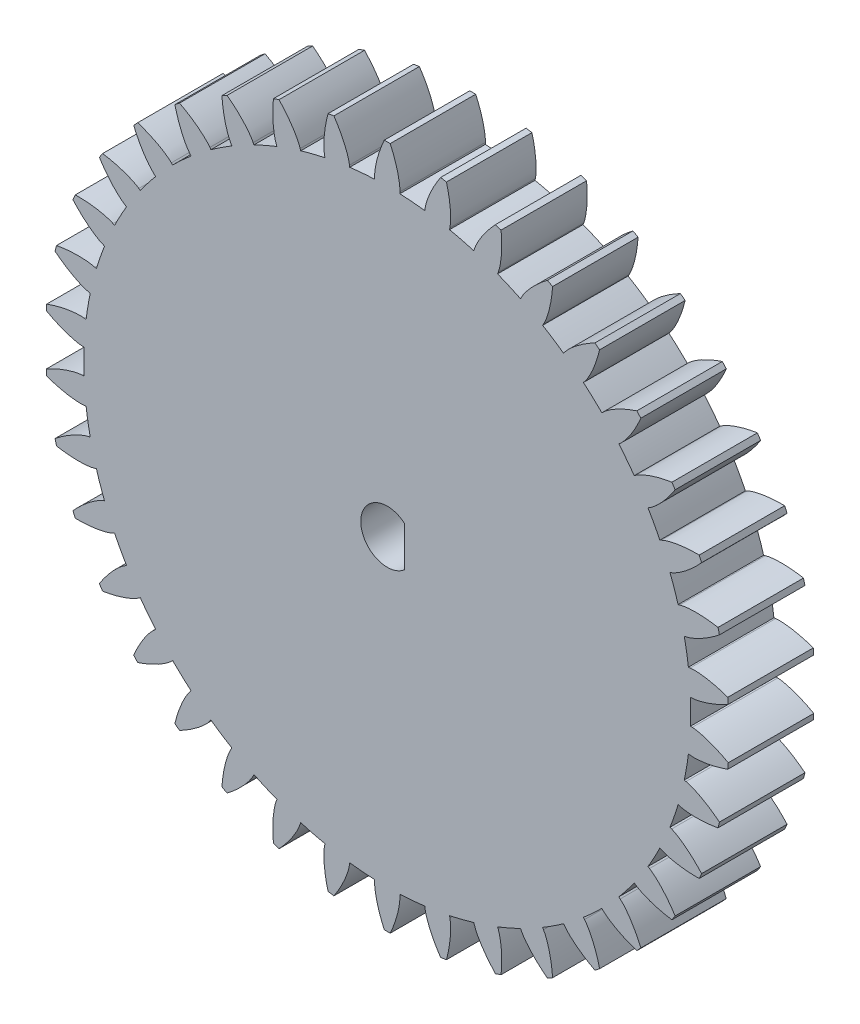
SolidWorks part; units mm, degrees
ref_plane "前视基准面" through (0, 0, 0) normal (0, 0, 1) x (1, 0, 0)
ref_plane "上视基准面" through (0, 0, 0) normal (0, 1, 0) x (1, 0, 0)
ref_plane "右视基准面" through (0, 0, 0) normal (1, 0, 0) x (0, 0, -1)
other "Configuration Table"
sketch "草图1" plane through (0, 0, 0) normal (0, 0, 1) x (1, 0, 0)
  line L0 (0, 0) -> (4, 0) construction
  line L1 (0, 0) -> (3.9231, 0.7804) construction
  line L2 (0, 0) -> (3.6941, 0.6945)
  line L3 (3.9231, 0.7804) -> (3.9231, -0.7804) construction
  line L4 (0, 0) -> (3.6941, -0.6945)
  circle A0 centre (0, 0) radius 5
  circle A1 centre (0, 0) radius 4 construction
  circle A2 centre (0, 0) radius 2.75
  circle A3 centre (0, 0) radius 3.7588 construction
  circle A4 centre (0, 0) radius 1.5
  spline S0 degree 4 poles (3.6941, 0.6945) (3.7222, 0.6998) (3.7997, 0.7204) (3.9403, 0.7826) (4.1522, 0.9137) (4.3976, 1.1246) (4.671, 1.4371) (4.933, 1.8476) (5.1531, 2.335) (5.3561, 3.0262) (5.443, 3.7431) (5.4253, 4.4924) (5.2827, 5.3729) (5.0281, 6.2292) (4.5902, 7.1708) (3.9479, 8.1289) (3.1749, 8.9843) (2.2938, 9.7273) (1.3255, 10.3516) (0.2887, 10.8537) (-0.7988, 11.2323) (-1.7817, 11.4556) (-2.5647, 11.5617) (-3.139, 11.6038) (-3.4958, 11.6181) (-3.788, 11.6215) (-4.0656, 11.6193) (-4.3699, 11.6068) (-4.6041, 11.5939) (-4.8725, 11.5704) (-5.1429, 11.5429) (-5.4129, 11.5084) (-5.885, 11.4372) (-6.2665, 11.3559) (-6.6616, 11.2688) (-6.8509, 11.2136) (-6.9779, 11.1808) knots 0 0 0 0 0 0.005604 0.015718 0.02996 0.048734 0.068727 0.096889 0.125051 0.153212 0.209535 0.237696 0.271429 0.327752 0.384075 0.440398 0.496721 0.553044 0.609367 0.66569 0.722013 0.778336 0.806497 0.820578 0.834659 0.84874 0.86282 0.876901 0.890982 0.900036 0.909091 0.931818 0.954545 0.977273 1 1 1 1 1 construction
  spline S1 degree 4 poles (3.6941, 0.6945) (3.7222, 0.6998) (3.7997, 0.7204) (3.9403, 0.7826) (4.1522, 0.9137) (4.3976, 1.1246) (4.671, 1.4371) (4.933, 1.8476) (5.1531, 2.335) (5.3561, 3.0262) (5.443, 3.7431) (5.4253, 4.4924) (5.2827, 5.3729) (5.0281, 6.2292) (4.5902, 7.1708) (3.9479, 8.1289) (3.1749, 8.9843) (2.2938, 9.7273) (1.3255, 10.3516) (0.2887, 10.8537) (-0.7988, 11.2323) (-1.7817, 11.4556) (-2.5647, 11.5617) (-3.139, 11.6038) (-3.4958, 11.6181) (-3.788, 11.6215) (-4.0656, 11.6193) (-4.3699, 11.6068) (-4.6041, 11.5939) (-4.8725, 11.5704) (-5.031, 11.5543) (-5.1147, 11.5449) (-5.1564, 11.5399) knots 0 0 0 0 0 0.005604 0.015718 0.02996 0.048734 0.068727 0.096889 0.125051 0.153212 0.209535 0.237696 0.271429 0.327752 0.384075 0.440398 0.496721 0.553044 0.609367 0.66569 0.722013 0.778336 0.806497 0.820578 0.834659 0.84874 0.86282 0.876901 0.890982 0.900036 0.909091 0.909091 0.909091 0.909091 0.909091
  spline S2 degree 4 poles (3.6941, -0.6945) (3.7222, -0.6998) (3.7997, -0.7204) (3.9403, -0.7826) (4.1522, -0.9137) (4.3976, -1.1246) (4.671, -1.4371) (4.933, -1.8476) (5.1531, -2.335) (5.3561, -3.0262) (5.443, -3.7431) (5.4253, -4.4924) (5.2827, -5.3729) (5.0281, -6.2292) (4.5902, -7.1708) (3.9479, -8.1289) (3.1749, -8.9843) (2.2938, -9.7273) (1.3255, -10.3516) (0.2887, -10.8537) (-0.7988, -11.2323) (-1.7817, -11.4556) (-2.5647, -11.5617) (-3.139, -11.6038) (-3.4958, -11.6181) (-3.788, -11.6215) (-4.0656, -11.6193) (-4.3699, -11.6068) (-4.6041, -11.5939) (-4.8725, -11.5704) (-5.1429, -11.5429) (-5.4129, -11.5084) (-5.885, -11.4372) (-6.2665, -11.3559) (-6.6616, -11.2688) (-6.8509, -11.2136) (-6.9779, -11.1808) knots 0 0 0 0 0 0.005604 0.015718 0.02996 0.048734 0.068727 0.096889 0.125051 0.153212 0.209535 0.237696 0.271429 0.327752 0.384075 0.440398 0.496721 0.553044 0.609367 0.66569 0.722013 0.778336 0.806497 0.820578 0.834659 0.84874 0.86282 0.876901 0.890982 0.900036 0.909091 0.931818 0.954545 0.977273 1 1 1 1 1 construction
  spline S3 degree 4 poles (3.6941, -0.6945) (3.7222, -0.6998) (3.7997, -0.7204) (3.9403, -0.7826) (4.1522, -0.9137) (4.3976, -1.1246) (4.671, -1.4371) (4.933, -1.8476) (5.1531, -2.335) (5.3561, -3.0262) (5.443, -3.7431) (5.4253, -4.4924) (5.2827, -5.3729) (5.0281, -6.2292) (4.5902, -7.1708) (3.9479, -8.1289) (3.1749, -8.9843) (2.2938, -9.7273) (1.3255, -10.3516) (0.2887, -10.8537) (-0.7988, -11.2323) (-1.7817, -11.4556) (-2.5647, -11.5617) (-3.139, -11.6038) (-3.4958, -11.6181) (-3.788, -11.6215) (-4.0656, -11.6193) (-4.3699, -11.6068) (-4.6041, -11.5939) (-4.8725, -11.5704) (-5.031, -11.5543) (-5.1147, -11.5449) (-5.1564, -11.5399) knots 0 0 0 0 0 0.005604 0.015718 0.02996 0.048734 0.068727 0.096889 0.125051 0.153212 0.209535 0.237696 0.271429 0.327752 0.384075 0.440398 0.496721 0.553044 0.609367 0.66569 0.722013 0.778336 0.806497 0.820578 0.834659 0.84874 0.86282 0.876901 0.890982 0.900036 0.909091 0.909091 0.909091 0.909091 0.909091
  point P15 (3.9231, 0)
  dimension "齿顶圆直径" = 10
  dimension "分度圆直径" = 8
  dimension "齿根圆直径" = 5.5
  dimension "基圆直径" = 7.5175
  dimension "内孔直径" = 3
  dimension "渐近线镜像线夹角" = 11.25
extrude "凸台-拉伸1" add sketch "草图1" along normal blind 5 contours A0 | A4
extrude "切除-拉伸1" cut sketch "草图1<3>" along normal through all contours A2 S3 A0 S1 region at (4.0533, 0, 0)
sketch "草图1<3>" plane through (0, 0, 0) normal (0, 0, 1) x (1, 0, 0) same geometry as "草图1"
fillet "圆角1" radius 0.5 4 edges at (2.7027, 0.5081, 2.5) (2.7027, -0.5081, 2.5) (4.7472, 1.5696, 2.5) (4.7472, -1.5696, 2.5)
pattern_circular "阵列(圆周)1" count 8 every 45 about axis through (0, 0, 5) along (0, 0, 1) of "切除-拉伸1", "圆角1"
sketch "草图2" plane through (0, 0, 5) normal (0, 0, 1) x (1, 0, 0)
  line L0 (0, 0) -> (19, 0) construction
  line L1 (0, 0) -> (17.8389, 0.7378)
  line L2 (0, 0) -> (17.8389, -0.7378)
  line L3 (17.8389, 0.7378) -> (17.8389, -0.7378) construction
  circle A0 centre (0, 0) radius 19 construction
  circle A1 centre (0, 0) radius 17.8542 construction
  circle A2 centre (0, 0) radius 17.75
  circle A3 centre (0, 0) radius 20
  circle A4 centre (0, 0) radius 1.5
  spline S0 degree 4 poles (17.8389, -0.7378) (17.8728, -0.7392) (17.9406, -0.7441) (18.0752, -0.7621) (18.3288, -0.8123) (18.6635, -0.9051) (19.1205, -1.0702) (19.658, -1.3153) (20.4669, -1.7609) (21.5195, -2.5027) (22.8507, -3.7145) (24.3091, -5.5094) (25.6114, -7.6908) (26.6766, -10.2121) (27.4216, -12.8444) (27.8645, -15.543) (28.0306, -18.4074) (27.8656, -21.9567) (27.1273, -26.1356) (25.5694, -30.8158) (23.0564, -35.6845) (20.2692, -39.5823) (17.5235, -42.6283) (15.0272, -44.9572) (12.9164, -46.6904) (10.7035, -48.2904) (8.3975, -49.7545) (5.4145, -51.4121) (1.6874, -53.1227) (-2.8247, -54.7082) (-7.1558, -55.7237) (-10.5228, -56.2445) (-12.9095, -56.489) (-14.244, -56.5948) (-15.5428, -56.66) (-16.5612, -56.6949) (-17.638, -56.7056) (-18.2041, -56.705) (-18.894, -56.6964) (-19.4423, -56.6837) (-20.126, -56.6612) (-20.9547, -56.6234) (-21.9141, -56.5638) (-23.0135, -56.4746) (-24.1084, -56.3645) (-25.2027, -56.2336) (-26.0203, -56.1199) (-26.5651, -56.0373) (-26.8369, -55.9943) knots 0 0 0 0 0 0.001401 0.002802 0.005604 0.010661 0.015718 0.022839 0.02996 0.048734 0.068727 0.096889 0.125051 0.153212 0.181374 0.209535 0.237696 0.271429 0.327752 0.384075 0.440398 0.496721 0.524883 0.553044 0.581206 0.609367 0.637529 0.66569 0.722013 0.778336 0.834659 0.84874 0.86282 0.876901 0.890982 0.900036 0.909091 0.914773 0.920455 0.926136 0.931818 0.943182 0.954545 0.965909 0.977273 0.988636 1 1 1 1 1 construction
  spline S1 degree 4 poles (17.8389, -0.7378) (17.8728, -0.7392) (17.9406, -0.7441) (18.0752, -0.7621) (18.3288, -0.8123) (18.6635, -0.9051) (19.1205, -1.0702) (19.658, -1.3153) (20.4669, -1.7609) (21.5195, -2.5027) (22.8507, -3.7145) (24.3091, -5.5094) (25.6114, -7.6908) (26.6766, -10.2121) (27.4216, -12.8444) (27.8645, -15.543) (28.0306, -18.4074) (27.8656, -21.9567) (27.1273, -26.1356) (25.5694, -30.8158) (23.0564, -35.6845) (20.2692, -39.5823) (17.5235, -42.6283) (15.0272, -44.9572) (12.9164, -46.6904) (10.7035, -48.2904) (8.3975, -49.7545) (5.4145, -51.4121) (1.6874, -53.1227) (-2.8247, -54.7082) (-7.1558, -55.7237) (-10.5228, -56.2445) (-12.9095, -56.489) (-14.244, -56.5948) (-15.5428, -56.66) (-16.5612, -56.6949) (-17.4764, -56.704) (-17.8641, -56.7049) (-18.0636, -56.7042) knots 0 0 0 0 0 0.001401 0.002802 0.005604 0.010661 0.015718 0.022839 0.02996 0.048734 0.068727 0.096889 0.125051 0.153212 0.181374 0.209535 0.237696 0.271429 0.327752 0.384075 0.440398 0.496721 0.524883 0.553044 0.581206 0.609367 0.637529 0.66569 0.722013 0.778336 0.834659 0.84874 0.86282 0.876901 0.890982 0.900036 0.909091 0.909091 0.909091 0.909091 0.909091
  spline S2 degree 4 poles (17.8389, 0.7378) (17.8728, 0.7392) (17.9406, 0.7441) (18.0752, 0.7621) (18.3288, 0.8123) (18.6635, 0.9051) (19.1205, 1.0702) (19.658, 1.3153) (20.4669, 1.7609) (21.5195, 2.5027) (22.8507, 3.7145) (24.3091, 5.5094) (25.6114, 7.6908) (26.6766, 10.2121) (27.4216, 12.8444) (27.8645, 15.543) (28.0306, 18.4074) (27.8656, 21.9567) (27.1273, 26.1356) (25.5694, 30.8158) (23.0564, 35.6845) (20.2692, 39.5823) (17.5235, 42.6283) (15.0272, 44.9572) (12.9164, 46.6904) (10.7035, 48.2904) (8.3975, 49.7545) (5.4145, 51.4121) (1.6874, 53.1227) (-2.8247, 54.7082) (-7.1558, 55.7237) (-10.5228, 56.2445) (-12.9095, 56.489) (-14.244, 56.5948) (-15.5428, 56.66) (-16.5612, 56.6949) (-17.638, 56.7056) (-18.2041, 56.705) (-18.894, 56.6964) (-19.4423, 56.6837) (-20.126, 56.6612) (-20.9547, 56.6234) (-21.9141, 56.5638) (-23.0135, 56.4746) (-24.1084, 56.3645) (-25.2027, 56.2336) (-26.0203, 56.1199) (-26.5651, 56.0373) (-26.8369, 55.9943) knots 0 0 0 0 0 0.001401 0.002802 0.005604 0.010661 0.015718 0.022839 0.02996 0.048734 0.068727 0.096889 0.125051 0.153212 0.181374 0.209535 0.237696 0.271429 0.327752 0.384075 0.440398 0.496721 0.524883 0.553044 0.581206 0.609367 0.637529 0.66569 0.722013 0.778336 0.834659 0.84874 0.86282 0.876901 0.890982 0.900036 0.909091 0.914773 0.920455 0.926136 0.931818 0.943182 0.954545 0.965909 0.977273 0.988636 1 1 1 1 1 construction
  spline S3 degree 4 poles (17.8389, 0.7378) (17.8728, 0.7392) (17.9406, 0.7441) (18.0752, 0.7621) (18.3288, 0.8123) (18.6635, 0.9051) (19.1205, 1.0702) (19.658, 1.3153) (20.4669, 1.7609) (21.5195, 2.5027) (22.8507, 3.7145) (24.3091, 5.5094) (25.6114, 7.6908) (26.6766, 10.2121) (27.4216, 12.8444) (27.8645, 15.543) (28.0306, 18.4074) (27.8656, 21.9567) (27.1273, 26.1356) (25.5694, 30.8158) (23.0564, 35.6845) (20.2692, 39.5823) (17.5235, 42.6283) (15.0272, 44.9572) (12.9164, 46.6904) (10.7035, 48.2904) (8.3975, 49.7545) (5.4145, 51.4121) (1.6874, 53.1227) (-2.8247, 54.7082) (-7.1558, 55.7237) (-10.5228, 56.2445) (-12.9095, 56.489) (-14.244, 56.5948) (-15.5428, 56.66) (-16.5612, 56.6949) (-17.4764, 56.704) (-17.8641, 56.7049) (-18.0636, 56.7042) knots 0 0 0 0 0 0.001401 0.002802 0.005604 0.010661 0.015718 0.022839 0.02996 0.048734 0.068727 0.096889 0.125051 0.153212 0.181374 0.209535 0.237696 0.271429 0.327752 0.384075 0.440398 0.496721 0.524883 0.553044 0.581206 0.609367 0.637529 0.66569 0.722013 0.778336 0.834659 0.84874 0.86282 0.876901 0.890982 0.900036 0.909091 0.909091 0.909091 0.909091 0.909091
  point P16 (17.8389, 0)
  dimension "内孔直径" = 3
  dimension "分度圆直径" = 38
  dimension "齿顶圆直径" = 40
  dimension "基圆直径" = 35.7083
  dimension "齿根圆直径" = 35.5
  dimension "渐开线镜像线夹角" = 2.368
extrude "凸台-拉伸2" add sketch "草图2" along normal blind 5 contours A3 | A4
extrude "切除-拉伸3" cut sketch "草图2<3>" along normal through all contours S3 L1 A2 L2 S1 A3 region at (19.0065, 0, 5)
sketch "草图2<3>" plane through (0, 0, 5) normal (0, 0, 1) x (1, 0, 0) same geometry as "草图2"
pattern_circular "阵列(圆周)2" count 38 over 360 about axis through (0, 0, 10) along (0, 0, 1) of "切除-拉伸3"
sketch "草图3" plane through (0, 0, 0) normal (0, 0, -1) x (-1, 0, 0)
  line L0 (-1, -1.1843) -> (-1, 1.1843)
  circle A0 centre (0, 0) radius 1.55
  dimension "D1" = 3.1
  dimension "D2" = 1
extrude "凸台-拉伸3" add sketch "草图3" against normal through all contours A0
extrude "切除-拉伸4" cut sketch "草图3<3>" against normal through all contours L0 region at (-0.1667, 0, 0)
sketch "草图3<3>" plane through (0, 0, 0) normal (0, 0, -1) x (-1, 0, 0) same geometry as "草图3"
equation "\"m\"= 1'模数"
equation "\"z\"= 8'齿数"
equation "\"a\"= 20度'压力角"
equation "\"d\"= \"m\" * \"z\"'分度圆直径"
equation "\"da\"= ( \"z\" + 2 ) * \"m\"'齿顶圆直径"
equation "\"df\"= ( \"z\" - 2.5 ) * \"m\"'齿根圆直径"
equation "\"s\"= 0.5 * PI * \"m\"'分度圆齿厚"
equation "\"r\"= 0.38 * \"m\"'齿根圆角"
equation "\"B\"= 0.3 * \"d\"'齿厚"
equation "\"db\"= \"m\" * \"z\" * cos ( \"a\" )'基圆直径"
equation "\"rb\"= \"db\" / 2'基圆半径"
equation "\"齿顶圆直径@草图1\"= \"da\""
equation "\"分度圆直径@草图1\"= \"d\""
equation "\"齿根圆直径@草图1\"= \"df\""
equation "\"基圆直径@草图1\"= \"db\""
equation "\"渐近线镜像线夹角@草图1\"= 360 / 4 / \"z\""
equation "\"h\"= 5'齿轮厚度"
equation "\"ir\"= 3'内孔直径"
equation "\"内孔直径@草图1\"= \"ir\""
equation "\"齿轮厚@凸台-拉伸1\"= \"h\""
equation "\"齿轮夹角@阵列(圆周)1\"= 360 / \"z\""
equation "\"齿数@阵列(圆周)1\"= \"z\""
equation "\"m1\"= 1'模数"
equation "\"z1\"= 38'齿数"
equation "\"a1\"= 20度'压力角"
equation "\"d1\"= \"m1\" * \"z1\"'分度圆直径"
equation "\"da1\"= ( \"z1\" + 2 ) * \"m1\"'齿顶圆直径"
equation "\"df1\"= ( \"z1\" - 2.5 ) * \"m1\"'齿根圆直径"
equation "\"s1\"= 0.5 * PI * \"m1\"'分度圆齿厚"
equation "\"r1\"= 0.38 * \"m1\"'齿根圆角"
equation "\"B1\"= 0.3 * \"d1\"'齿厚"
equation "\"db1\"= \"m1\" * \"z1\" * cos ( \"a1\" )'基圆直径"
equation "\"rb1\"= \"db1\" / 2'基圆半径"
equation "\"分度圆直径@草图2\"= \"d1\""
equation "\"齿顶圆直径@草图2\"= \"da1\""
equation "\"基圆直径@草图2\"= \"db1\""
equation "\"齿根圆直径@草图2\"= \"df1\""
equation "\"渐开线镜像线夹角@草图2\"= 360 / 4 / \"z1\""
equation "\"内孔直径@草图2\"= \"ir\""
equation "\"二层齿轮厚@凸台-拉伸2\" = \"h1\""
equation "\"h1\"= 5'齿轮厚度"
equation "\"二层齿数@阵列(圆周)2\"= \"z1\""
